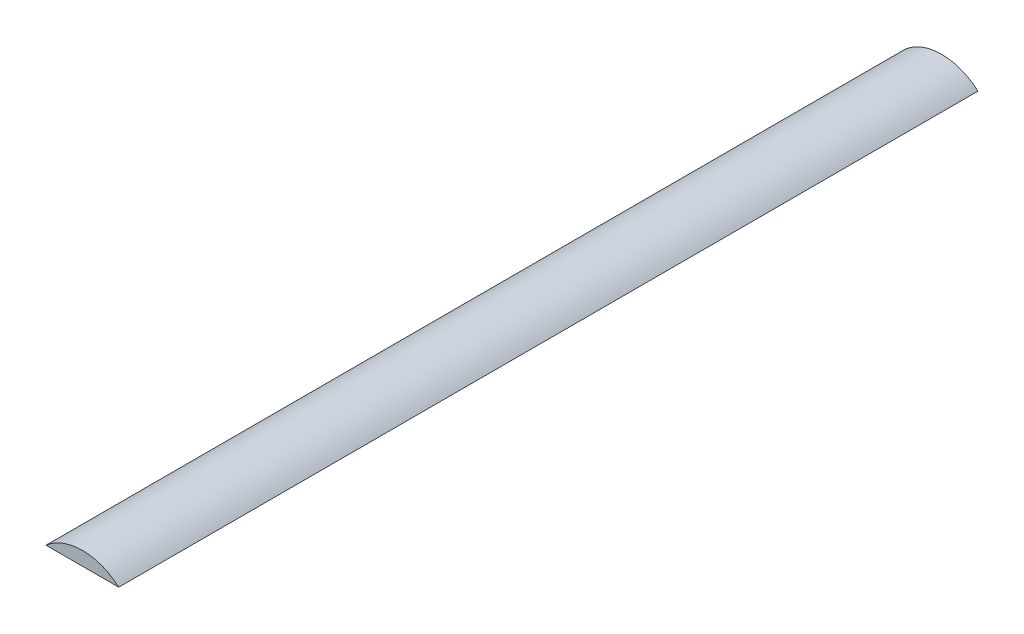
SolidWorks part; units mm, degrees
ref_plane "前视基准面" through (0, 0, 0) normal (0, 0, 1) x (1, 0, 0)
ref_plane "上视基准面" through (0, 0, 0) normal (0, 1, 0) x (1, 0, 0)
ref_plane "右视基准面" through (0, 0, 0) normal (1, 0, 0) x (0, 0, -1)
other "Configuration Table"
sketch "草图1" plane through (0, 0, 0) normal (0, 0, 1) x (1, 0, 0)
  line L1 (5, 5) -> (5, 1) construction
  line L2 (5, 1) -> (-5.583, 1)
  line L3 (5, 1) -> (15.583, 1)
  arc A0 (-5.583, 1) -> (15.583, 1) centre (5, -11) cw
  dimension "D1" = 16
  dimension "D2" = 4
extrude "凸台-拉伸1" add sketch "草图1" along normal blind 250
